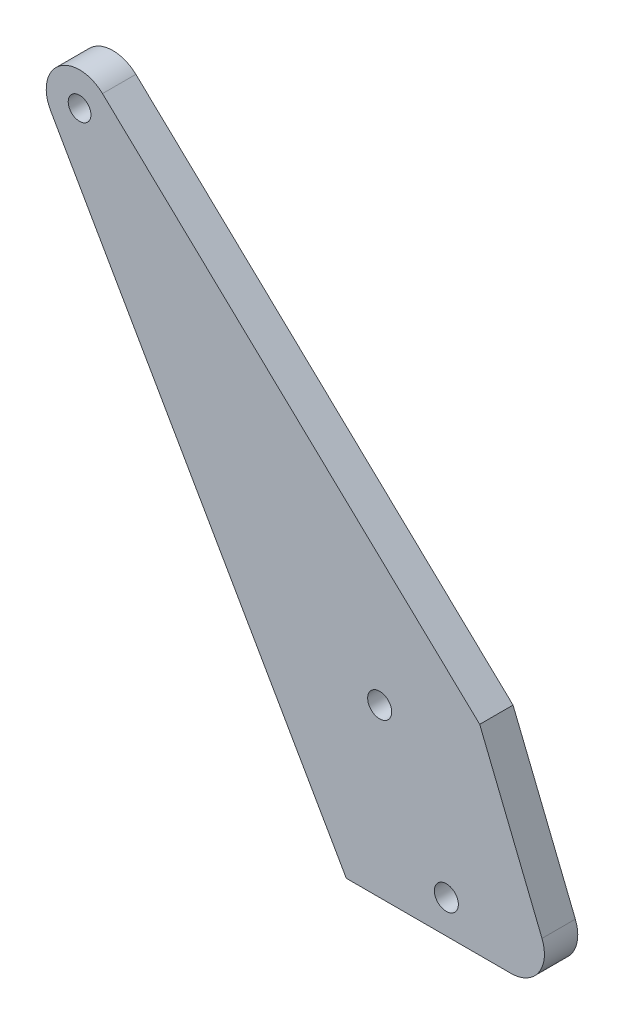
SolidWorks part; units mm, degrees
ref_plane "Front Plane" through (0, 0, 0) normal (0, 0, 1) x (1, 0, 0)
ref_plane "Top Plane" through (0, 0, 0) normal (0, 1, 0) x (1, 0, 0)
ref_plane "Right Plane" through (0, 0, 0) normal (1, 0, 0) x (0, 0, -1)
sketch "Sketch1" plane through (0, 0, 0) normal (0, 0, 1) x (1, 0, 0)
  line L1 (0, 0) -> (-25.4, 0)
  line L6 (-71.8309, 106.208) -> (0, 38.1)
  line L7 (-81.712, 98.4471) -> (-25.4, 0)
  line L8 (-323.85, -215.9) -> (44.45, -215.9) construction
  line L9 (0, 38.1) -> (15.3934, 0)
  line L10 (15.3934, 0) -> (0, 0)
  line L11 (0, 38.1) -> (0, 0) construction
  arc A1 (-71.8309, 106.208) -> (-81.712, 98.4471) centre (-76.2, 101.6) ccw
  circle A2 centre (-6.35, 6.35) radius 2.286
  circle A3 centre (-19.05, 31.75) radius 2.286
  circle A4 centre (-76.2, 101.6) radius 2.159
  dimension "D3" = 76.2
  dimension "D5" = 12.7
  dimension "D7" = 4.572
  dimension "D4" = 6.35
  dimension ".17" = 4.318
  dimension "D1" = 25.4
  dimension "D2" = 38.1
  dimension "D6" = 317.5
  dimension "D8" = 31.75
  dimension "D9" = 19.05
  dimension "D11" = 6.35
  dimension "D12" = 22
extrude "Boss-Extrude1" add sketch "Sketch1" against normal blind 6.35
fillet "Fillet1" radius 6.35 1 edges at (15.3934, 0, -3.175)
